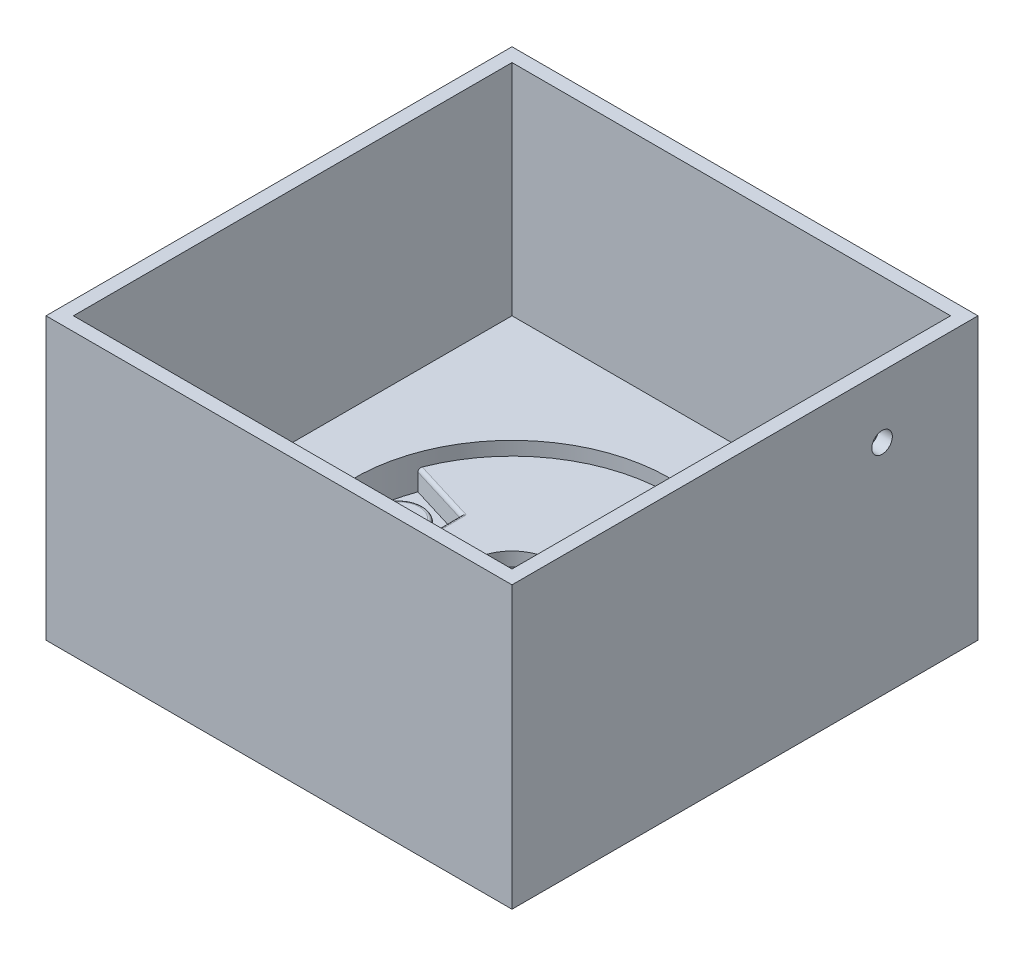
SolidWorks part; units mm, degrees
ref_plane "Front Plane" through (0, 0, 0) normal (0, 0, 1) x (1, 0, 0)
ref_plane "Top Plane" through (0, 0, 0) normal (0, 1, 0) x (1, 0, 0)
ref_plane "Right Plane" through (0, 0, 0) normal (1, 0, 0) x (0, 0, -1)
sketch "Sketch1" plane through (0, 0, 0) normal (0, 1, 0) x (1, 0, 0)
  line L1 (-34, -34) -> (34, -34)
  line L2 (-34, -34) -> (-34, 34)
  line L3 (-34, 34) -> (34, 34)
  line L4 (34, -34) -> (34, 34)
  line L5 (-34, -34) -> (34, 34) construction
  line L6 (-34, 34) -> (34, -34) construction
  point P0 (0, 0)
  dimension "D1" = 68
extrude "Boss-Extrude1" add sketch "Sketch1" along normal blind 41
sketch "Sketch2" plane through (0, 0, 0) normal (0, 1, 0) x (1, 0, 0)
  line L1 (-32, -32) -> (32, -32)
  line L2 (-32, -32) -> (-32, 32)
  line L3 (-32, 32) -> (32, 32)
  line L4 (32, -32) -> (32, 32)
  line L5 (-32, -32) -> (32, 32) construction
  line L6 (-32, 32) -> (32, -32) construction
  point P0 (0, 0)
  dimension "D1" = 64
extrude "Cut-Extrude1" cut sketch "Sketch2" against normal blind 32 from surface starting at face at (0, 41, 0)
sketch "Sketch3" plane through (0, 0, 0) normal (0, 1, 0) x (1, 0, 0)
  circle A0 centre (0, 0) radius 23
  dimension "D1" = 46
extrude "Cut-Extrude4" cut sketch "Sketch3" against normal blind 2 from surface starting at face at (0, 9, 0)
sketch "Sketch4" plane through (0, 7, 0) normal (0, 1, 0) x (1, 0, 0)
  line L2 (-19.9206, -1.095) -> (-22.9685, -1.2027)
  line L3 (-19.9903, 1.0511) -> (-22.9701, 1.1719)
  line L8 (-21.6098, -7.8752) -> (-12.5558, -4.8686)
  line L9 (-21.6093, 7.8764) -> (-12.6699, 5.1333)
  line L11 (-12.5558, -4.8686) -> (-12.6699, 5.1333)
  arc A0 (-21.6093, 7.8764) -> (-22.9701, 1.1719) centre (0, 0) ccw
  arc A1 (-22.9685, -1.2027) -> (-21.6098, -7.8752) centre (0, 0) ccw
  circle A2 centre (0, 0) radius 23 construction
  arc A10 (-19.9206, -1.095) -> (-19.9903, 1.0511) centre (-16.6259, 0.0862) ccw
extrude "Cut-Extrude6" cut sketch "Sketch4" against normal blind 3
sketch "Sketch5" plane through (0, 0, 0) normal (0, 1, 0) x (1, 0, 0)
  circle A0 centre (0, 0) radius 6.05
  dimension "D1" = 12.1
extrude "Cut-Extrude9" cut sketch "Sketch5" against normal through all from surface starting at face at (-5.9588, 7, -0.0662)
sketch "Sketch6" plane through (0, 0, 0) normal (0, -1, 0) x (1, 0, 0)
  circle A0 centre (0, 0) radius 10.5
  dimension "D1" = 21
extrude "Cut-Extrude10" cut sketch "Sketch6" against normal blind 5 from surface starting at face at (0, 0, 6.05)
sketch "Sketch7" plane through (0, 0, 0) normal (0, -1, 0) x (-1, 0, 0)
  line L0 (-34, 34) -> (34, -34) construction
  line L1 (-34, -34) -> (34, 34) construction
  line L3 (-15.025, 15.025) -> (15.025, 15.025)
  line L4 (-15.025, 15.025) -> (-15.025, -15.025)
  line L5 (-15.025, -15.025) -> (15.025, -15.025)
  line L6 (15.025, 15.025) -> (15.025, -15.025)
  line L7 (-13.025, 13.025) -> (13.025, 13.025)
  line L8 (-13.025, 13.025) -> (-13.025, -13.025)
  line L9 (-13.025, -13.025) -> (13.025, -13.025)
  line L10 (13.025, 13.025) -> (13.025, -13.025)
  point P8 (0, 0)
  dimension "D1" = 30.05
  dimension "D2" = 26.05
extrude "Cut-Extrude11" cut sketch "Sketch7" against normal blind 2
sketch "Sketch8" plane through (32, 0, 0) normal (-1, 0, 0) x (0, 0, 1)
  line L0 (32, 9) -> (-32, 9) construction
  line L1 (-32, 9) -> (-32, 41) construction
  circle A0 centre (-20, 32) radius 1.5
  dimension "D1" = 3
  dimension "D2" = 23
  dimension "D3" = 12
extrude "Cut-Extrude12" cut sketch "Sketch8" against normal through all
fillet "Fillet1" radius 0.5 6 edges at (-21.4802, 7, -1.1115) (-21.4446, 7, 1.1488) (-13.1277, 7, -0.1998) (-17.0828, 7, 6.3719) (-12.6128, 7, -0.1323) (-17.1396, 7, -6.5048)
fillet "Fillet2" radius 0.5 8 edges at (0, 0, 13.025) (-13.025, 0, 0) (13.025, 0, 0) (0, 0, -13.025) (-15.025, 0, 0) (0, 0, 15.025) (15.025, 0, 0) (0, 0, -15.025)
